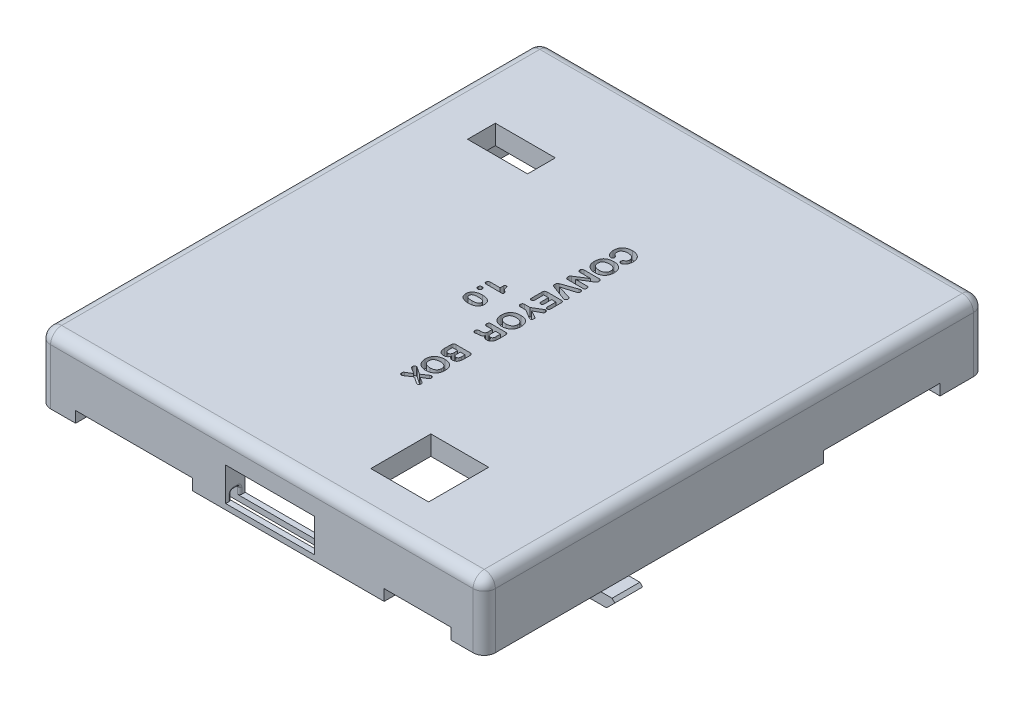
SolidWorks part; units mm, degrees
material "ABS"
ref_plane "Alzado" through (0, 0, 0) normal (0, 0, 1) x (1, 0, 0)
ref_plane "Planta" through (0, 0, 0) normal (0, 1, 0) x (1, 0, 0)
ref_plane "Vista lateral" through (0, 0, 0) normal (1, 0, 0) x (0, 0, -1)
sketch "Croquis1" plane through (0, 0, 0) normal (0, 1, 0) x (1, 0, 0)
  line L1 (-40, 45) -> (40, 45)
  line L2 (-40, 45) -> (-40, -45)
  line L3 (-40, -45) -> (40, -45)
  line L4 (40, 45) -> (40, -45)
  line L5 (-40, 45) -> (40, -45) construction
  line L6 (-40, -45) -> (40, 45) construction
  point P0 (0, 0)
  dimension "D1" = 90
  dimension "D2" = 80
extrude "Saliente-Extruir1" add sketch "Croquis1" along normal blind 28
fillet "Redondeo1" radius 2 12 edges at (0, 28, -45) (40, 28, 0) (0, 28, 45) (-40, 28, 0) (0, 0, 45) (0, 0, -45) (40, 0, 0) (-40, 0, 0) (-40, 14, 45) (40, 14, 45) (40, 14, -45) (-40, 14, -45)
shell "Vaciado2" thickness 3.5
sketch "Croquis3" plane through (0, 0, 45) normal (0, 0, 1) x (1, 0, 0)
  line L1 (-33.5, 18) -> (-12.5, 18)
  line L2 (-33.5, 18) -> (-33.5, 4)
  line L3 (-33.5, 4) -> (-12.5, 4)
  line L4 (-12.5, 18) -> (-12.5, 4)
  line L5 (40, 28) -> (40, 0) construction
  line L6 (22, 18) -> (34, 18)
  line L7 (22, 18) -> (22, 4)
  line L8 (22, 4) -> (34, 4)
  line L9 (34, 18) -> (34, 4)
  line L10 (-40, 28) -> (-40, 0) construction
  line L11 (-38, 2) -> (38, 2) construction
  line L12 (-6.5, 23) -> (9.5, 23)
  line L13 (-6.5, 23) -> (-6.5, 17)
  line L14 (-6.5, 17) -> (9.5, 17)
  line L15 (9.5, 23) -> (9.5, 17)
  dimension "D1" = 14
  dimension "D2" = 12
  dimension "D3" = 6
  dimension "D4" = 6.5
  dimension "D5" = 21
  dimension "D6" = 14
  dimension "D7" = 6
  dimension "D8" = 6
  dimension "D9" = 16
  dimension "D10" = 2
  dimension "D11" = 15
sketch "Croquis4" plane through (-40, 0, 0) normal (-1, 0, 0) x (0, 0, 1)
  line L1 (-23, 18) -> (-2, 18)
  line L2 (-23, 18) -> (-23, 4)
  line L3 (-23, 4) -> (-2, 4)
  line L4 (-2, 18) -> (-2, 4)
  line L5 (-45, 28) -> (-45, 0) construction
  line L6 (45, 28) -> (45, 0) construction
  line L7 (-43, 2) -> (43, 2) construction
  dimension "D1" = 14
  dimension "D2" = 21
  dimension "D3" = 22
  dimension "D4" = 47
  dimension "D5" = 2
sketch "Croquis5" plane through (40, 0, 0) normal (1, 0, 0) x (0, 0, -1)
  line L0 (-43, 2) -> (43, 2) construction
  line L1 (16, 18) -> (37, 18)
  line L2 (16, 18) -> (16, 4)
  line L3 (16, 4) -> (37, 4)
  line L4 (37, 18) -> (37, 4)
  line L5 (45, 28) -> (45, 0) construction
  dimension "D1" = 14
  dimension "D2" = 8
  dimension "D3" = 21
  dimension "D4" = 2
sketch "Croquis6" plane through (0, 3.5, 0) normal (0, 1, 0) x (1, 0, 0)
  line L2 (0, 0) -> (0, 18.5567) construction
  line L3 (0, 0) -> (-1.7547, 0) construction
  circle A8 centre (-24.776, 36.449) radius 1.25
  circle A9 centre (19.304, 36.449) radius 1.25
  circle A10 centre (-8.636, -19.431) radius 1.25
  circle A11 centre (15.494, -19.431) radius 1.25
  dimension "D1" = 2.5
  dimension "D2" = 36.449
  dimension "D3" = 24.776
  dimension "D5" = 19.431
  dimension "D4" = 44.08
  dimension "D6" = 8.636
  dimension "D7" = 24.13
extrude "Saliente-Extruir2" add sketch "Croquis6" along normal blind 8
extrude "Cortar-Extruir1" cut sketch "Croquis3" against normal up to next
extrude "Cortar-Extruir2" cut sketch "Croquis4" against normal up to next
extrude "Cortar-Extruir3" cut sketch "Croquis5" against normal up to next
ref_plane "Plano1" through (0, 16, 0) normal (0, 1, 0) x (1, 0, 0)
split "Partir1" trim tools "Plano1" bodies to split 112 resulting bodies 113 114
sketch "Croquis7" plane through (40, 0, 0) normal (1, 0, 0) x (0, 0, -1)
  line L0 (-19, 16) -> (-19, 12) construction
  line L1 (-43, 16) -> (16, 16) construction
  line L3 (-43, 16) -> (-43, 2) construction
  line L5 (-22, 13.5) -> (-16, 13.5)
  line L6 (-22, 13.5) -> (-22, 10.5)
  line L7 (-22, 10.5) -> (-16, 10.5)
  line L8 (-16, 13.5) -> (-16, 10.5)
  line L9 (-22, 13.5) -> (-16, 10.5) construction
  line L10 (-22, 10.5) -> (-16, 13.5) construction
  dimension "D1" = 24
  dimension "D2" = 3
  dimension "D3" = 6
  dimension "D4" = 4
extrude "Cortar-Extruir4" cut sketch "Croquis7" against normal up to next (3.5 mm away)
ref_plane "Plano2" through (0, 0, 21.5) normal (0, 0, -1) x (-1, 0, 0)
sketch "Croquis9" plane through (0, 0, 21.5) normal (0, 0, -1) x (-1, 0, 0)
  line L0 (-40.5, 13.5) -> (-36.5, 13.5)
  line L1 (-36.5, 13.5) -> (-36.5, 21.5)
  line L2 (-36.5, 16) -> (-36.5, 3.5) construction
  line L3 (-36.5, 21.5) -> (-34.5, 21.5)
  line L4 (-34.5, 21.5) -> (-34.5, 11.5)
  line L5 (-34.5, 11.5) -> (-40.5, 11.5)
  line L7 (-40.5, 11.5) -> (-40.5, 13.5)
  dimension "D1" = 2
  dimension "D2" = 2
  dimension "D3" = 10
  dimension "D4" = 6
extrude "Saliente-Extruir3" add sketch "Croquis9" along normal blind 5
chamfer "Chaflán1" distance 2 angle 45 1 edges at (40.5, 11.5, 19)
chamfer "Chaflán2" distance 1 angle 45 1 edges at (40.5, 13.5, 19)
chamfer "Chaflán3" distance 2 angle 45 1 edges at (34.5, 21.5, 19)
fillet "Redondeo2" radius 0.5 1 edges at (36.5, 13.5, 19)
fillet "Redondeo3" radius 0.5 1 edges at (36.5, 13.5, 19)
mirror "Simetría2" about plane through (0, 0, 0) normal (1, 0, 0) of "Cortar-Extruir4"
fillet "Redondeo4" radius 0.5 1 edges at (-36.5, 13.5, 19)
mirror "Simetría3" about plane through (0, 0, 0) normal (1, 0, 0) of "Redondeo2", "Chaflán3", "Chaflán2", "Chaflán1", "Saliente-Extruir3"
sketch "Croquis10" plane through (0, 16, 0) normal (0, 1, 0) x (1, 0, 0)
  line L24 (-38.75, 43) -> (-38.75, 24.25)
  line L25 (-38.75, 24.25) -> (-37.75, 24.25)
  line L26 (-37.75, 24.25) -> (-37.75, 42.75)
  line L27 (-37.75, 42.75) -> (37.75, 42.75)
  line L28 (37.75, 42.75) -> (37.75, 38.25)
  line L29 (37.75, 38.25) -> (38.75, 38.25)
  line L30 (38.75, 38.25) -> (38.75, 43)
  line L31 (38, 43.75) -> (-38, 43.75)
  line L32 (-38.75, 43) -> (-38.75, 24.25)
  line L33 (-38.75, 24.25) -> (-37.75, 24.25)
  line L34 (-37.75, 24.25) -> (-37.75, 42.75)
  line L35 (-37.75, 42.75) -> (37.75, 42.75)
  line L36 (37.75, 42.75) -> (37.75, 38.25)
  line L37 (37.75, 38.25) -> (38.75, 38.25)
  line L38 (38.75, 38.25) -> (38.75, 43)
  line L39 (38, 43.75) -> (-38, 43.75)
  line L44 (37.75, -42.75) -> (35.25, -42.75)
  line L45 (35.25, -42.75) -> (35.25, -43.75)
  line L46 (35.25, -43.75) -> (38, -43.75)
  line L47 (38.75, -43) -> (38.75, 14.75)
  line L48 (38.75, 14.75) -> (37.75, 14.75)
  line L49 (37.75, 14.75) -> (37.75, -42.75)
  line L50 (37.75, -42.75) -> (35.25, -42.75)
  line L51 (35.25, -42.75) -> (35.25, -43.75)
  line L52 (35.25, -43.75) -> (38, -43.75)
  line L53 (38.75, -43) -> (38.75, 14.75)
  line L54 (38.75, 14.75) -> (37.75, 14.75)
  line L55 (37.75, 14.75) -> (37.75, -42.75)
  line L58 (20.75, -42.75) -> (-11.25, -42.75)
  line L59 (-11.25, -42.75) -> (-11.25, -43.75)
  line L60 (-11.25, -43.75) -> (20.75, -43.75)
  line L61 (20.75, -43.75) -> (20.75, -42.75)
  line L62 (20.75, -42.75) -> (-11.25, -42.75)
  line L63 (-11.25, -42.75) -> (-11.25, -43.75)
  line L64 (-11.25, -43.75) -> (20.75, -43.75)
  line L65 (20.75, -43.75) -> (20.75, -42.75)
  line L74 (-34.75, -42.75) -> (-37.75, -42.75)
  line L75 (-37.75, -42.75) -> (-37.75, 0.75)
  line L76 (-37.75, 0.75) -> (-38.75, 0.75)
  line L77 (-38.75, 0.75) -> (-38.75, -43)
  line L78 (-38, -43.75) -> (-34.75, -43.75)
  line L79 (-34.75, -43.75) -> (-34.75, -42.75)
  line L80 (-34.75, -42.75) -> (-37.75, -42.75)
  line L81 (-37.75, -42.75) -> (-37.75, 0.75)
  line L82 (-37.75, 0.75) -> (-38.75, 0.75)
  line L83 (-38.75, 0.75) -> (-38.75, -43)
  line L84 (-38, -43.75) -> (-34.75, -43.75)
  line L85 (-34.75, -43.75) -> (-34.75, -42.75)
  arc A6 (-38, 43.75) -> (-38.75, 43) centre (-38, 43) ccw
  arc A7 (38.75, 43) -> (38, 43.75) centre (38, 43) ccw
  arc A8 (-38, 43.75) -> (-38.75, 43) centre (-38, 43) ccw
  arc A9 (38.75, 43) -> (38, 43.75) centre (38, 43) ccw
  arc A10 (38, -43.75) -> (38.75, -43) centre (38, -43) ccw
  arc A11 (38, -43.75) -> (38.75, -43) centre (38, -43) ccw
  arc A13 (-38.75, -43) -> (-38, -43.75) centre (-38, -43) ccw
  arc A14 (-38.75, -43) -> (-38, -43.75) centre (-38, -43) ccw
  dimension "D1" = 1.25
  dimension "D2" = 1.25
  dimension "D3" = 1.25
  dimension "D4" = 1.25
extrude "Saliente-Extruir4" add sketch "Croquis10" along normal blind 2
fillet "Redondeo6" radius 0.4 20 edges at (-38.75, 18, 21.125) (-38.5303, 18, 43.5303) (36.625, 18, 43.75) (38.5303, 18, 43.5303) (36.5, 18, 42.75) (-36.25, 18, 42.75) (-37.75, 18, 21) (-36.375, 18, 43.75) (4.75, 18, 42.75) (4.75, 18, 43.75) (37.75, 18, 14) (38.75, 18, 14.125) (-38.75, 18, -33.625) (-38.5303, 18, -43.5303) (0, 18, -43.75) (38.5303, 18, -43.5303) (-37.75, 18, -33.5) (37.75, 18, -40.5) (38.75, 18, -40.625) (0, 18, -42.75)
sketch "Croquis11" plane through (0, 16, 0) normal (0, -1, 0) x (1, 0, 0)
  line L16 (35, 42.5) -> (37.5, 42.5)
  line L17 (37.5, 42.5) -> (37.5, 21.5)
  line L18 (37.5, 21.5) -> (37.5, 16.5)
  line L19 (37.5, 16.5) -> (37.5, -15)
  line L20 (37.5, -15) -> (39, -15)
  line L21 (39, -15) -> (39, 43)
  line L22 (38, 44) -> (35, 44)
  line L23 (35, 44) -> (35, 42.5)
  line L24 (35, 42.5) -> (37.5, 42.5)
  line L25 (37.5, 42.5) -> (37.5, 21.5)
  line L26 (37.5, 21.5) -> (37.5, 16.5)
  line L27 (37.5, 16.5) -> (37.5, -15)
  line L28 (37.5, -15) -> (39, -15)
  line L29 (39, -15) -> (39, 43)
  line L30 (38, 44) -> (35, 44)
  line L31 (35, 44) -> (35, 42.5)
  line L32 (-11.5, 42.5) -> (21, 42.5)
  line L33 (21, 42.5) -> (21, 44)
  line L34 (21, 44) -> (-11.5, 44)
  line L35 (-11.5, 44) -> (-11.5, 42.5)
  line L36 (-11.5, 42.5) -> (21, 42.5)
  line L37 (21, 42.5) -> (21, 44)
  line L38 (21, 44) -> (-11.5, 44)
  line L39 (-11.5, 44) -> (-11.5, 42.5)
  line L44 (-37.5, 42.5) -> (-34.5, 42.5)
  line L45 (-34.5, 42.5) -> (-34.5, 44)
  line L46 (-34.5, 44) -> (-38, 44)
  line L47 (-39, 43) -> (-39, -1)
  line L48 (-39, -1) -> (-37.5, -1)
  line L49 (-37.5, -1) -> (-37.5, 16.5)
  line L50 (-37.5, 16.5) -> (-37.5, 21.5)
  line L51 (-37.5, 21.5) -> (-37.5, 42.5)
  line L52 (-37.5, 42.5) -> (-34.5, 42.5)
  line L53 (-34.5, 42.5) -> (-34.5, 44)
  line L54 (-34.5, 44) -> (-38, 44)
  line L55 (-39, 43) -> (-39, -1)
  line L56 (-39, -1) -> (-37.5, -1)
  line L57 (-37.5, -1) -> (-37.5, 16.5)
  line L58 (-37.5, 16.5) -> (-37.5, 21.5)
  line L59 (-37.5, 21.5) -> (-37.5, 42.5)
  line L68 (-38, -44) -> (38, -44)
  line L69 (39, -43) -> (39, -38)
  line L70 (39, -38) -> (37.5, -38)
  line L71 (37.5, -38) -> (37.5, -42.5)
  line L72 (37.5, -42.5) -> (-37.5, -42.5)
  line L73 (-37.5, -42.5) -> (-37.5, -24)
  line L74 (-37.5, -24) -> (-39, -24)
  line L75 (-39, -24) -> (-39, -43)
  line L76 (-38, -44) -> (38, -44)
  line L77 (39, -43) -> (39, -38)
  line L78 (39, -38) -> (37.5, -38)
  line L79 (37.5, -38) -> (37.5, -42.5)
  line L80 (37.5, -42.5) -> (-37.5, -42.5)
  line L81 (-37.5, -42.5) -> (-37.5, -24)
  line L82 (-37.5, -24) -> (-39, -24)
  line L83 (-39, -24) -> (-39, -43)
  arc A2 (39, 43) -> (38, 44) centre (38, 43) ccw
  arc A3 (39, 43) -> (38, 44) centre (38, 43) ccw
  arc A4 (-38, 44) -> (-39, 43) centre (-38, 43) ccw
  arc A5 (-38, 44) -> (-39, 43) centre (-38, 43) ccw
  arc A9 (-39, -43) -> (-38, -44) centre (-38, -43) ccw
  arc A10 (38, -44) -> (39, -43) centre (38, -43) ccw
  arc A11 (-39, -43) -> (-38, -44) centre (-38, -43) ccw
  arc A12 (38, -44) -> (39, -43) centre (38, -43) ccw
  dimension "D1" = 1
  dimension "D2" = 1
  dimension "D3" = 1
  dimension "D4" = 1
extrude "Cortar-Extruir5" cut sketch "Croquis11" against normal blind 2.5
fillet "Redondeo7" radius 0.4 36 edges at (-6.5, 17.75, 42.5) (-6.5, 17.75, 44) (9.5, 17.75, 44) (9.5, 17.75, 42.5) (39, 18.5, -40.5) (38.7071, 18.5, -43.7071) (0, 18.5, -44) (-38.7071, 18.5, -43.7071) (-39, 18.5, 21) (-38.7071, 18.5, 43.7071) (-9, 18.5, 42.5) (-11.5, 18.5, 43.25) (-9, 18.5, 44) (-6.5, 18.5, 43.25) (15.25, 18.5, 44) (21, 18.5, 43.25) (15.25, 18.5, 42.5) (9.5, 18.5, 43.25) (36.5, 18.5, 44) (38.7071, 18.5, 43.7071) (39, 18.5, 14) (38.25, 18.5, -15) (37.5, 18.5, 13.75) (36.25, 18.5, 42.5) (35, 18.5, 43.25) (38.25, 18.5, -38) (37.5, 18.5, -40.25) (0, 18.5, -42.5) (-39, 18.5, -33.5) (-37.5, 18.5, -33.25) (-38.25, 18.5, -24) (-38.25, 18.5, -1) (-36.25, 18.5, 44) (-34.5, 18.5, 43.25) (-36, 18.5, 42.5) (-37.5, 18.5, 20.75)
sketch "Croquis12" plane through (0, 28, 0) normal (0, 1, 0) x (1, 0, 0)
  line L0 (38, -43) -> (38, 43) construction
  line L1 (12.1, -26.7) -> (22.5, -26.7)
  line L2 (12.1, -26.7) -> (12.1, -37.5)
  line L3 (12.1, -37.5) -> (22.5, -37.5)
  line L4 (22.5, -26.7) -> (22.5, -37.5)
  line L5 (36.5, -41.5) -> (-36.5, -41.5) construction
  line L6 (-38, 43) -> (-38, -43) construction
  line L7 (-30.5, 27.5) -> (-19.7, 27.5)
  line L8 (-30.5, 27.5) -> (-30.5, 22.5)
  line L9 (-30.5, 22.5) -> (-19.7, 22.5)
  line L10 (-19.7, 27.5) -> (-19.7, 22.5)
  line L11 (38, 43) -> (-38, 43) construction
  dimension "D1" = 10.4
  dimension "D2" = 10.8
  dimension "D3" = 15.5
  dimension "D4" = 4
  dimension "D5" = 10.8
  dimension "D6" = 5
  dimension "D7" = 7.5
  dimension "D8" = 15.5
extrude "Cortar-Extruir6" cut sketch "Croquis12" against normal up to next (3.5 mm away)
sketch "Croquis13" plane through (0, 28, 0) normal (0, 1, 0) x (1, 0, 0)
  line L0 (0, 34.8306) -> (0, -34.8306) construction
  text T0 "CONVEYOR  BOX\r\n1.0" font "Helvetica Rounded" height 3.5
  point P4 (0, 0)
extrude "Cortar-Extruir7" cut sketch "Croquis13" against normal blind 1.5
delete or keep bodies "Sólido-Eliminar/Conservar 1" type delete bodies bodies 124
